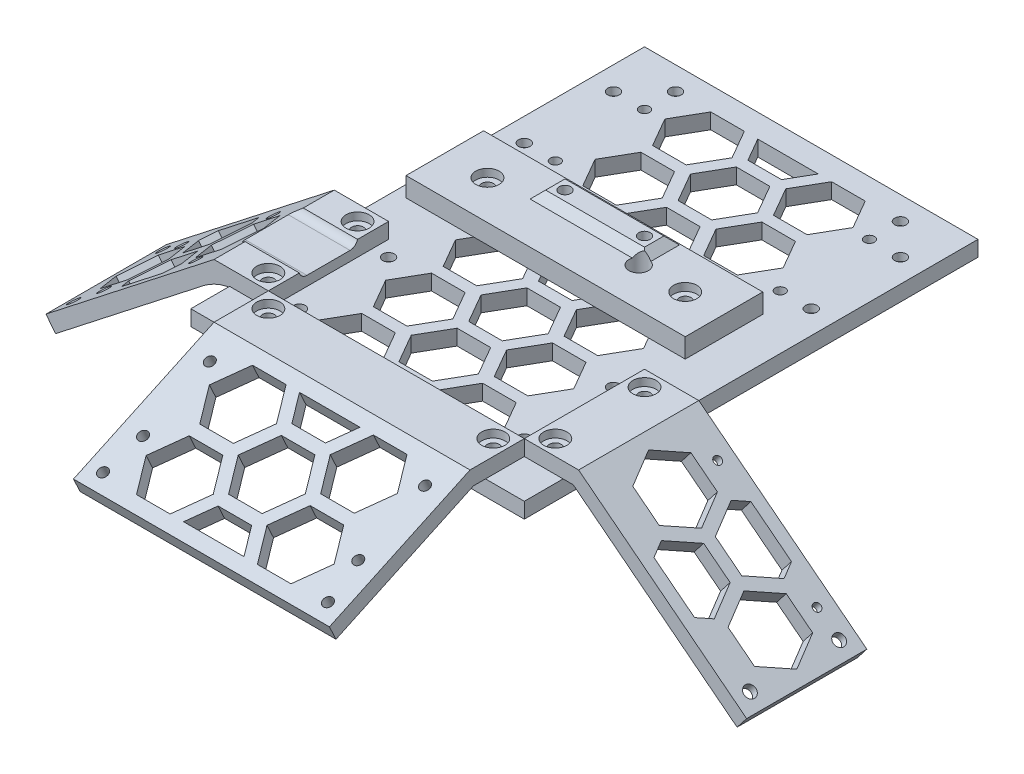
SolidWorks part; units mm, degrees
ref_plane "Front Plane" through (0, 0, 0) normal (0, 0, 1) x (1, 0, 0)
ref_plane "Top Plane" through (0, 0, 0) normal (0, 1, 0) x (1, 0, 0)
ref_plane "Right Plane" through (0, 0, 0) normal (1, 0, 0) x (0, 0, -1)
sketch "Sketch1" plane through (0, 0, 0) normal (0, 1, 0) x (1, 0, 0)
  line L0 (0, 0) -> (-19, 0) construction
  line L1 (0, 0) -> (23, 0) construction
  circle A0 centre (-25, 0) radius 6
  circle A1 centre (26, 0) radius 3
  dimension "D1" = 12
  dimension "D2" = 6
  dimension "D3" = 23
  dimension "D4" = 19
sketch "Sketch2" plane through (0, 0, 0) normal (0, 1, 0) x (1, 0, 0)
  line L0 (-36, 10) -> (-36, -10)
  line L1 (-36, -10) -> (36, -10)
  line L2 (36, -10) -> (36, 10)
  line L3 (36, 10) -> (-36, 10)
  line L4 (-31, 0) -> (-36, 0) construction
  line L5 (-36, -3.9429) -> (36, -3.9429) construction
  line L6 (0, 0) -> (-19, 0) construction
  line L7 (0, 0) -> (23, 0) construction
  circle A0 centre (-25, 0) radius 6 construction
  point P18 (0, -3.9429)
  dimension "D1" = 10
  dimension "D2" = 10
  dimension "D3" = 5
extrude "Boss-Extrude1" add sketch "Sketch2" along normal blind 5
extrude "Boss-Extrude2" add sketch "Sketch1" against normal blind 4
sketch "Sketch3" plane through (0, -4, 0) normal (0, -1, 0) x (1, 0, 0)
  circle A0 centre (-25, 0) radius 1.5
  circle A1 centre (26, 0) radius 1.5
  circle A2 centre (26, 0) radius 3 construction
  circle A3 centre (-25, 0) radius 6 construction
  dimension "D1" = 3
extrude "Cut-Extrude1" cut sketch "Sketch3" against normal through all
sketch "Sketch4" plane through (0, 5, 0) normal (0, 1, 0) x (1, 0, 0)
  circle A0 centre (-25, 0) radius 3
  circle A1 centre (26, 0) radius 3
  dimension "D1" = 6
extrude "Cut-Extrude2" cut sketch "Sketch4" against normal blind 2
sketch "Sketch5" plane through (0, 0, 0) normal (0, -1, 0) x (1, 0, 0)
  circle A0 centre (26, 0) radius 3
  circle A1 centre (26, 0) radius 4
  circle A2 centre (26, 0) radius 3 construction
  dimension "D1" = 8
extrude "Boss-Extrude3" [suppressed] add sketch "Sketch5" along normal blind 2.5
sketch "Sketch6" plane through (0, -4, 0) normal (0, -1, 0) x (1, 0, 0)
  line L0 (-36, 48.5) -> (-36, -48.5) construction
  line L1 (-36, -48.5) -> (36, -48.5) construction
  line L2 (36, -48.5) -> (36, 48.5) construction
  line L3 (36, 48.5) -> (-36, 48.5) construction
  line L4 (-36, 18.5) -> (36, 18.5) construction
  line L5 (-36, -18.5) -> (36, -18.5) construction
  line L6 (-36, -48.5) -> (-36, -58.5) construction
  line L7 (0, 18.5) -> (0, -18.5) construction
  line L8 (-36, 0) -> (36, 0) construction
  line L9 (-36, -10) -> (-36, 10) construction
  line L10 (-36, -58.5) -> (36, -58.5)
  line L11 (36, -58.5) -> (36, -48.5) construction
  line L12 (-36, 48.5) -> (-36, 58.5) construction
  line L13 (-36, 58.5) -> (36, 58.5)
  line L14 (36, 58.5) -> (36, 48.5) construction
  line L15 (-36, 58.5) -> (-43, 58.5)
  line L16 (-43, 58.5) -> (-43, -58.5)
  line L17 (-43, -58.5) -> (-36, -58.5)
  line L18 (36, -58.5) -> (43, -58.5)
  line L19 (43, -58.5) -> (43, 58.5)
  line L20 (43, 58.5) -> (36, 58.5)
  circle A0 centre (-29, -21.5) radius 1.3
  circle A2 centre (-29, -44.5) radius 1.3
  circle A3 centre (29, -44.5) radius 1.3
  circle A4 centre (29, -21.5) radius 1.3
  circle A5 centre (29, 21.5) radius 1.3 construction
  circle A6 centre (29, 44.5) radius 1.3 construction
  circle A7 centre (-29, 44.5) radius 1.3 construction
  circle A8 centre (-29, 21.5) radius 1.3 construction
  circle A9 centre (-25, 0) radius 1.5
  circle A10 centre (26, 0) radius 1.5
  circle A11 centre (26, 0) radius 1.5 construction
  circle A12 centre (-25, 0) radius 1.5 construction
  circle A13 centre (-29, 44.5) radius 1.5
  circle A14 centre (-29, 21.5) radius 1.5
  circle A15 centre (29, 21.5) radius 1.5
  circle A16 centre (29, 44.5) radius 1.5
  circle A17 centre (-29, 52.5) radius 1.5
  circle A18 centre (29, 52.5) radius 1.5
  circle A19 centre (29, -52.5) radius 1.5
  circle A20 centre (-29, -52.5) radius 1.5
  circle A21 centre (-37, 44.5) radius 1.5
  circle A22 centre (-37, 21.5) radius 1.5
  circle A23 centre (37, 44.5) radius 1.5
  circle A24 centre (37, 21.5) radius 1.5
  circle A25 centre (37, -44.5) radius 1.5
  circle A26 centre (37, -21.5) radius 1.5
  circle A27 centre (-37, -21.5) radius 1.5
  circle A28 centre (-37, -44.5) radius 1.5
  point P10 (0, 0)
  dimension "D2" = 29
  dimension "D4" = 2.6
  dimension "D5" = 23
  dimension "D8" = 3
  dimension "D11" = 3
  dimension "D13" = 7
  dimension "D15" = 8
  dimension "D1" = 37
  dimension "D3" = 3
  dimension "D6" = 4
  dimension "D7" = 4
  dimension "D9" = 10
  dimension "D10" = 10
  dimension "D14" = 8
extrude "Boss-Extrude4" add sketch "Sketch6" along normal blind 4 separate body
sketch "Sketch8" plane through (0, 0, 0) normal (0, -1, 0) x (1, 0, 0)
  circle A0 centre (14, 0) radius 2.5
  circle A1 centre (26, 0) radius 3 construction
  dimension "D1" = 5
  dimension "D2" = 12
extrude "Cut-Extrude3" cut sketch "Sketch8" against normal through all
sketch "Sketch10" plane through (0, 5, 0) normal (0, 1, 0) x (1, 0, 0)
  line L0 (-8.75, 5.25) -> (8.75, 5.25) construction
  line L1 (13, -7.5) -> (-13, -7.5) construction
  line L2 (13, -7.5) -> (13, 7.5) construction
  line L3 (13, 7.5) -> (-13, 7.5) construction
  line L4 (-13, -7.5) -> (-13, 7.5) construction
  line L5 (13, -7.5) -> (-13, 7.5) construction
  line L6 (13, 7.5) -> (-13, -7.5) construction
  line L7 (0, 5.25) -> (0, 0) construction
  line L8 (-8.75, 5.25) -> (-11.75, 5.25) construction
  line L9 (8.75, 5.25) -> (11.75, 5.25) construction
  line L10 (-10.25, 3.75) -> (-10.25, -7.5) construction
  line L11 (-10.25, 6.75) -> (-10.25, 7.5) construction
  line L12 (-11.75, 5.25) -> (-13, 5.25) construction
  circle A0 centre (-10.25, 5.25) radius 1.5
  circle A1 centre (10.25, 5.25) radius 1.5
  point P0 (0, 0)
  dimension "D3" = 23.5
  dimension "D4" = 3
  dimension "D5" = 3
  dimension "D1" = 26
  dimension "D2" = 15
  dimension "D6" = 11.25
extrude "Cut-Extrude4" cut sketch "Sketch10" against normal up to surface (5 mm away) up to face at (14, 0, -2.5)
sketch "Sketch11" plane through (0, 5, 0) normal (0, 1, 0) x (1, 0, 0)
  line L0 (-12.75, 7.75) -> (-12.75, 2.75)
  line L1 (-12.75, 2.75) -> (12.75, 2.75)
  line L2 (12.75, 2.75) -> (12.75, 7.75)
  line L3 (12.75, 7.75) -> (-12.75, 7.75)
  line L4 (0, 2.75) -> (0, 0) construction
  circle A0 centre (-10.25, 5.25) radius 1.5 construction
  circle A1 centre (10.25, 5.25) radius 1.5 construction
  circle A2 centre (-10.25, 5.25) radius 1.5
  circle A3 centre (10.25, 5.25) radius 1.5
  dimension "D1" = 2.5
  dimension "D2" = 2.5
  dimension "D3" = 2.5
extrude "Boss-Extrude6" add sketch "Sketch11" along normal blind 2
chamfer "Chamfer2" distance 2 angle 45 4 edges at (0, 5, -2.75) (12.75, 5, -5.25) (0, 5, -7.75) (-12.75, 5, -5.25)
sketch "Sketch12" plane through (0, 0, 0) normal (0, -1, 0) x (1, 0, 0)
  circle A0 centre (-10.25, -5.25) radius 3
  circle A1 centre (10.25, -5.25) radius 3
  dimension "D1" = 6
  dimension "D2" = 6
extrude "Cut-Extrude5" cut sketch "Sketch12" against normal blind 2
sketch "Sketch14" plane through (0, -8, 0) normal (0, -1, 0) x (1, 0, 0)
  line L0 (-37, 47.4831) -> (-31.9831, 47.4831)
  line L1 (-37, 41.5169) -> (-29, 41.5169)
  line L2 (-31.9831, 47.4831) -> (-31.9831, 52.5)
  line L3 (-26.0169, 44.5) -> (-26.0169, 52.5)
  line L4 (-37, 24.4831) -> (-29, 24.4831)
  line L5 (-37, 18.5169) -> (-29, 18.5169)
  line L6 (-43, 0) -> (43, 0) construction
  line L11 (0, 58.5) -> (0, -58.5) construction
  line L12 (43, 58.5) -> (-43, 58.5) construction
  line L13 (-43, -58.5) -> (43, -58.5) construction
  line L14 (37, 18.5169) -> (29, 18.5169)
  line L15 (37, 24.4831) -> (29, 24.4831)
  line L16 (26.0169, 44.5) -> (26.0169, 52.5)
  line L17 (31.9831, 47.4831) -> (31.9831, 52.5)
  line L18 (37, 41.5169) -> (29, 41.5169)
  line L19 (37, 47.4831) -> (31.9831, 47.4831)
  line L20 (37, -47.4831) -> (31.9831, -47.4831)
  line L21 (37, -41.5169) -> (29, -41.5169)
  line L22 (31.9831, -47.4831) -> (31.9831, -52.5)
  line L23 (26.0169, -44.5) -> (26.0169, -52.5)
  line L24 (37, -24.4831) -> (29, -24.4831)
  line L25 (37, -18.5169) -> (29, -18.5169)
  line L26 (-37, -18.5169) -> (-29, -18.5169)
  line L27 (-37, -24.4831) -> (-29, -24.4831)
  line L28 (-26.0169, -44.5) -> (-26.0169, -52.5)
  line L29 (-31.9831, -47.4831) -> (-31.9831, -52.5)
  line L30 (-37, -41.5169) -> (-29, -41.5169)
  line L31 (-37, -47.4831) -> (-31.9831, -47.4831)
  line L32 (-43, 58.5) -> (-43, -58.5) construction
  arc A0 (-29, 41.5169) -> (-26.0169, 44.5) centre (-29, 44.5) ccw
  arc A1 (-26.0169, 52.5) -> (-31.9831, 52.5) centre (-29, 52.5) ccw
  arc A2 (-37, 47.4831) -> (-37, 41.5169) centre (-37, 44.5) ccw
  arc A6 (-29, 18.5169) -> (-29, 24.4831) centre (-29, 21.5) ccw
  arc A7 (-37, 24.4831) -> (-37, 18.5169) centre (-37, 21.5) ccw
  circle A10 centre (-25, 0) radius 2.9831
  circle A11 centre (26, 0) radius 2.9831
  arc A12 (37, 24.4831) -> (37, 18.5169) centre (37, 21.5) cw
  arc A13 (29, 18.5169) -> (29, 24.4831) centre (29, 21.5) cw
  arc A14 (37, 47.4831) -> (37, 41.5169) centre (37, 44.5) cw
  arc A15 (26.0169, 52.5) -> (31.9831, 52.5) centre (29, 52.5) cw
  arc A16 (29, 41.5169) -> (26.0169, 44.5) centre (29, 44.5) cw
  arc A17 (29, -41.5169) -> (26.0169, -44.5) centre (29, -44.5) ccw
  arc A18 (26.0169, -52.5) -> (31.9831, -52.5) centre (29, -52.5) ccw
  arc A19 (37, -47.4831) -> (37, -41.5169) centre (37, -44.5) ccw
  arc A20 (29, -18.5169) -> (29, -24.4831) centre (29, -21.5) ccw
  arc A21 (37, -24.4831) -> (37, -18.5169) centre (37, -21.5) ccw
  arc A22 (-37, -24.4831) -> (-37, -18.5169) centre (-37, -21.5) cw
  arc A23 (-29, -18.5169) -> (-29, -24.4831) centre (-29, -21.5) cw
  arc A24 (-37, -47.4831) -> (-37, -41.5169) centre (-37, -44.5) cw
  arc A25 (-26.0169, -52.5) -> (-31.9831, -52.5) centre (-29, -52.5) cw
  arc A26 (-29, -41.5169) -> (-26.0169, -44.5) centre (-29, -44.5) cw
extrude "Cut-Extrude6" cut sketch "Sketch14" against normal blind 2
sketch "Sketch15" plane through (0, -4, 0) normal (0, 1, 0) x (1, 0, 0)
  line L0 (-33, -17.5) -> (-33, -48.5)
  line L1 (-33, -48.5) -> (-47, -48.5)
  line L2 (-47, -48.5) -> (-47, -17.5)
  line L3 (-47, -17.5) -> (-33, -17.5)
  line L4 (-43, -58.5) -> (-43, 58.5) construction
  circle A0 centre (-37, -21.5) radius 1.5
  circle A1 centre (-37, -44.5) radius 1.5
  circle A2 centre (-37, -21.5) radius 1.5 construction
  circle A3 centre (-37, -44.5) radius 1.5 construction
  dimension "D1" = 4
  dimension "D2" = 4
  dimension "D3" = 4
  dimension "D4" = 4
extrude "Boss-Extrude7" add sketch "Sketch15" along normal blind 4 separate body
sketch "Sketch17" plane through (0, 0, 48.5) normal (0, 0, 1) x (1, 0, 0)
  line L0 (-47, 0) -> (-90.3406, -33.8614)
  line L1 (-90.3406, -33.8614) -> (-87.8779, -37.0134)
  line L2 (-87.8779, -37.0134) -> (-45.6227, -4)
  line L3 (-47, -4) -> (-33, -4) construction
  line L4 (-45.6227, -4) -> (-47, 0)
  dimension "D1" = 38
  dimension "D2" = 4
  dimension "D3" = 55
extrude "Boss-Extrude8" add sketch "Sketch17" against normal up to surface (31 mm away) up to face at (-40, -2, 17.5)
sketch "Sketch18" plane through (0, 0, 0) normal (0, 1, 0) x (1, 0, 0)
  circle A0 centre (-37, -21.5) radius 3
  circle A1 centre (-37, -44.5) radius 3
  dimension "D1" = 6
  dimension "D2" = 6
extrude "Cut-Extrude7" cut sketch "Sketch18" against normal blind 2
sketch "Sketch19" plane through (-17.8148, 22.8019, 0) normal (-0.6157, 0.788, 0) x (0.788, 0.6157, 0)
  line L0 (-37.0365, -17.5) -> (-37.0365, -48.5) construction
  line L1 (-80.0365, -23) -> (-50.0365, -23) construction
  line L2 (-80.0365, -23) -> (-80.0365, -43) construction
  line L3 (-80.0365, -43) -> (-50.0365, -43) construction
  line L4 (-50.0365, -23) -> (-50.0365, -43) construction
  line L5 (-80.0365, -23) -> (-50.0365, -43) construction
  line L6 (-80.0365, -43) -> (-50.0365, -23) construction
  line L7 (-88.0365, -21.5) -> (-29.2057, -21.5) construction
  line L8 (-88.0365, -44.5) -> (-29.2057, -44.5) construction
  line L9 (-92.0365, -17.5) -> (-92.0365, -48.5) construction
  circle A0 centre (-50.0365, -23) radius 1.5
  circle A1 centre (-50.0365, -43) radius 1.5
  circle A2 centre (-80.0365, -43) radius 1.5
  circle A3 centre (-80.0365, -23) radius 1.5
  circle A4 centre (-88.0365, -21.5) radius 1.5
  circle A5 centre (-88.0365, -44.5) radius 1.5
  ellipse E1 centre (-30.3877, -21.5) end of major axis (-30.3877, -23) minor radius 1.182 construction
  ellipse E2 centre (-30.3877, -44.5) end of major axis (-30.3877, -46) minor radius 1.182 construction
  point P0 (-65.0365, -33)
  point P7 (-37.0365, -33)
  dimension "D3" = 3
  dimension "D5" = 3
  dimension "D1" = 30
  dimension "D2" = 20
  dimension "D4" = 28
  dimension "D6" = 4
extrude "Cut-Extrude8" cut sketch "Sketch19" against normal through all
sketch "Sketch20" plane through (-15.3522, 19.6499, 0) normal (0.6157, -0.788, 0) x (0.788, 0.6157, 0)
  line L0 (-88.5894, 24.4486) -> (-80.5894, 25.9486)
  line L1 (-87.4836, 18.5514) -> (-79.4836, 20.0514)
  line L2 (-88.5894, 41.5514) -> (-80.5894, 40.0514)
  line L3 (-87.4836, 47.4486) -> (-79.4836, 45.9486)
  arc A0 (-87.4836, 47.4486) -> (-88.5894, 41.5514) centre (-88.0365, 44.5) ccw
  arc A1 (-88.5894, 24.4486) -> (-87.4836, 18.5514) centre (-88.0365, 21.5) ccw
  arc A2 (-79.4836, 20.0514) -> (-80.5894, 25.9486) centre (-80.0365, 23) ccw
  arc A3 (-80.5894, 40.0514) -> (-79.4836, 45.9486) centre (-80.0365, 43) ccw
  circle A4 centre (-50.0365, 43) radius 3
  circle A5 centre (-50.0365, 23) radius 3
  dimension "D1" = 6
  dimension "D2" = 6
  dimension "D3" = 6
  dimension "D4" = 6
  dimension "D5" = 6
extrude "Cut-Extrude9" cut sketch "Sketch20" against normal blind 2
sketch "Sketch21" plane through (0, -4, 0) normal (0, 1, 0) x (1, 0, 0)
  line L0 (-33, -48.5) -> (-33, -62.5)
  line L1 (-33, -62.5) -> (33, -62.5)
  line L2 (33, -62.5) -> (33, -48.5)
  line L3 (33, -48.5) -> (-33, -48.5)
  line L5 (43, -58.5) -> (-43, -58.5) construction
  circle A0 centre (-29, -52.5) radius 1.5 construction
  circle A2 centre (29, -52.5) radius 1.5 construction
  circle A3 centre (-29, -52.5) radius 1.5
  circle A4 centre (29, -52.5) radius 1.5
  dimension "D3" = 4
  dimension "D1" = 4
  dimension "D2" = 4
  dimension "D4" = 4
extrude "Boss-Extrude9" add sketch "Sketch21" along normal blind 4 separate body
sketch "Sketch22" plane through (0, 0, 0) normal (0, 1, 0) x (1, 0, 0)
  circle A0 centre (-29, -52.5) radius 3
  circle A1 centre (29, -52.5) radius 3
  dimension "D1" = 6
  dimension "D2" = 6
extrude "Cut-Extrude10" cut sketch "Sketch22" against normal blind 2
sketch "Sketch23" plane through (-33, 0, 0) normal (-1, 0, 0) x (0, 0, 1)
  line L0 (62.5, 0) -> (98.7523, -16.9047)
  line L1 (98.7523, -16.9047) -> (97.0618, -20.53)
  line L2 (97.0618, -20.53) -> (61.6132, -4)
  line L3 (48.5, -4) -> (62.5, -4) construction
  line L5 (61.6132, -4) -> (62.5, 0)
  dimension "D1" = 4
  dimension "D2" = 25
  dimension "D3" = 40
extrude "Boss-Extrude10" add sketch "Sketch23" against normal up to surface (66 mm away) up to face at (33, -2, 55.5)
sketch "Sketch25" plane through (0, 0, 0) normal (0, 1, 0) x (1, 0, 0)
  line L0 (-33, -25.5) -> (-90.3406, -25.5)
  line L1 (-33, -48.5) -> (-33, -17.5) construction
  line L2 (-90.3406, -17.5) -> (-90.3406, -48.5) construction
  line L3 (-90.3406, -25.5) -> (-90.3406, -40.5)
  line L4 (-90.3406, -40.5) -> (-33, -40.5)
  line L5 (-33, -40.5) -> (-33, -25.5)
  circle A0 centre (-37, -21.5) radius 3 construction
  circle A1 centre (-37, -44.5) radius 3 construction
  dimension "D1" = 4
  dimension "D2" = 4
extrude "Cut-Extrude11" cut sketch "Sketch25" against normal blind 1.5
fillet "Fillet1" radius 2 2 edges at (-40.96, -1.5, 40.5) (-40.96, -1.5, 25.5)
fillet "Fillet2" radius 15 1 edges at (-45.6227, -4, 33)
sketch "Sketch28" plane through (0, 23.9389, 11.1629) normal (0, 0.9063, 0.4226) x (1, 0, 0)
  line L0 (33, -96.6442) -> (-33, -96.6442) construction
  line L1 (-29, -47.0669) -> (-29, -92.6442) construction
  line L2 (0, -43.9559) -> (0, -96.6442) construction
  line L3 (33, -43.9559) -> (-33, -43.9559) construction
  line L4 (-33, -56.6442) -> (33, -56.6442) construction
  line L5 (-27.75, -63.6442) -> (27.75, -63.6442) construction
  line L6 (-27.75, -63.6442) -> (-27.75, -82.6442) construction
  line L7 (-27.75, -82.6442) -> (27.75, -82.6442) construction
  line L8 (27.75, -63.6442) -> (27.75, -82.6442) construction
  line L9 (-27.75, -63.6442) -> (27.75, -82.6442) construction
  line L10 (-27.75, -82.6442) -> (27.75, -63.6442) construction
  circle A0 centre (-29, -92.6442) radius 1.25
  circle A1 centre (29, -92.6442) radius 1.25
  circle A2 centre (-27.75, -63.6442) radius 1.25
  circle A3 centre (-27.75, -82.6442) radius 1.25
  circle A4 centre (27.75, -82.6442) radius 1.25
  circle A5 centre (27.75, -63.6442) radius 1.25
  ellipse E0 centre (-29, -48.4264) end of major axis (-27.5, -48.4264) minor radius 1.3595 construction
  point P17 (0, -73.1442)
  dimension "D1" = 4
  dimension "D2" = 2.5
  dimension "D5" = 2.5
  dimension "D3" = 55.5
  dimension "D4" = 19
  dimension "D6" = 7
extrude "Cut-Extrude12" cut sketch "Sketch28" against normal up to surface (4 mm away) up to face at (0, -12.265, 79.3375)
sketch "Sketch29" plane through (0, 23.9389, 11.1629) normal (0, 0.9063, 0.4226) x (1, 0, 0)
  line L0 (-33, -76.6442) -> (33, -76.6442) construction
  line L1 (-6.9282, -67.6442) -> (-11.2583, -60.1442)
  line L2 (-11.2583, -60.1442) -> (-19.9186, -60.1442)
  line L3 (-19.9186, -60.1442) -> (-24.2487, -67.6442)
  line L4 (-24.2487, -67.6442) -> (-19.9186, -75.1442)
  line L5 (-19.9186, -75.1442) -> (-11.2583, -75.1442)
  line L6 (-11.2583, -75.1442) -> (-6.9282, -67.6442)
  line L7 (24.2487, -67.6442) -> (19.9186, -60.1442)
  line L8 (19.9186, -60.1442) -> (11.2583, -60.1442)
  line L9 (11.2583, -60.1442) -> (6.9282, -67.6442)
  line L10 (6.9282, -67.6442) -> (11.2583, -75.1442)
  line L11 (11.2583, -75.1442) -> (19.9186, -75.1442)
  line L12 (19.9186, -75.1442) -> (24.2487, -67.6442)
  line L13 (8.6603, -76.6442) -> (4.3301, -69.1442)
  line L14 (4.3301, -69.1442) -> (-4.3301, -69.1442)
  line L15 (-4.3301, -69.1442) -> (-8.6603, -76.6442)
  line L16 (-8.6603, -76.6442) -> (-4.3301, -84.1442)
  line L17 (-4.3301, -84.1442) -> (4.3301, -84.1442)
  line L18 (4.3301, -84.1442) -> (8.6603, -76.6442)
  line L19 (24.2487, -85.6442) -> (19.9186, -78.1442)
  line L20 (19.9186, -78.1442) -> (11.2583, -78.1442)
  line L21 (11.2583, -78.1442) -> (6.9282, -85.6442)
  line L22 (6.9282, -85.6442) -> (11.2583, -93.1442)
  line L23 (11.2583, -93.1442) -> (19.9186, -93.1442)
  line L24 (19.9186, -93.1442) -> (24.2487, -85.6442)
  line L25 (-6.9282, -85.6442) -> (-11.2583, -78.1442)
  line L26 (-11.2583, -78.1442) -> (-19.9186, -78.1442)
  line L27 (-19.9186, -78.1442) -> (-24.2487, -85.6442)
  line L28 (-24.2487, -85.6442) -> (-19.9186, -93.1442)
  line L29 (-19.9186, -93.1442) -> (-11.2583, -93.1442)
  line L30 (-11.2583, -93.1442) -> (-6.9282, -85.6442)
  line L31 (-33, -96.6442) -> (-33, -56.6442) construction
  line L32 (33, -56.6442) -> (33, -96.6442) construction
  line L33 (-7.7942, -93.1442) -> (7.7942, -93.1442)
  line L34 (7.7942, -93.1442) -> (4.3301, -87.1442)
  line L35 (4.3301, -87.1442) -> (-4.3301, -87.1442)
  line L36 (-4.3301, -87.1442) -> (-7.7942, -93.1442)
  line L40 (-7.7942, -60.1442) -> (7.7942, -60.1442)
  line L41 (-8.6603, -94.6442) -> (-6.4952, -98.3942) [skipped]
  line L42 (4.3301, -102.1442) -> (6.4952, -98.3942) [skipped]
  line L43 (-4.3301, -102.1442) -> (0, -102.1442) [skipped]
  line L44 (-4.3301, -66.1442) -> (-7.7942, -60.1442)
  line L45 (4.3301, -66.1442) -> (-4.3301, -66.1442)
  line L46 (7.7942, -60.1442) -> (4.3301, -66.1442)
  circle A0 centre (-15.5885, -67.6442) radius 7.5 construction
  circle A1 centre (15.5885, -67.6442) radius 7.5 construction
  circle A2 centre (0, -76.6442) radius 7.5 construction
  circle A3 centre (15.5885, -85.6442) radius 7.5 construction
  circle A4 centre (-15.5885, -85.6442) radius 7.5 construction
  arc A6 (7.3485, -93.1442) -> (-7.3485, -93.1442) centre (0, -94.6442) ccw construction
  dimension "D1" = 15
  dimension "D8" = 3
  dimension "D2" = 3
  dimension "D3" = 1.5
  dimension "D4" = 3
  dimension "D5" = 3
  dimension "D6" = 3
  dimension "D7" = 3
  dimension "D9" = 3
  dimension "D10" = 3
  dimension "D11" = 3
extrude "Cut-Extrude13" cut sketch "Sketch29" against normal up to surface (4 mm away) up to face at (27.75, -14.085, 83.2406)
sketch "Sketch30" plane through (0, -4, 0) normal (0, 1, 0) x (1, 0, 0)
  line L0 (33, -48.5) -> (47, -48.5)
  line L1 (47, -48.5) -> (47, -17.5)
  line L2 (47, -17.5) -> (33, -17.5)
  line L3 (33, -17.5) -> (33, -48.5)
  line L4 (-33, -17.5) -> (-47, -17.5) construction
  circle A0 centre (37, -21.5) radius 1.5
  circle A2 centre (37, -44.5) radius 1.5
  circle A4 centre (-37, -44.5) radius 1.5 construction
extrude "Boss-Extrude11" add sketch "Sketch30" along normal blind 4 separate body
sketch "Sketch31" plane through (0, 0, 48.5) normal (0, 0, 1) x (1, 0, 0)
  line L0 (47, 0) -> (90.3406, -33.8614)
  line L1 (90.3406, -33.8614) -> (87.8779, -37.0134)
  line L2 (87.8779, -37.0134) -> (45.6227, -4)
  line L3 (33, -4) -> (47, -4) construction
  line L4 (47, 0) -> (45.6227, -4)
  line L5 (-90.3406, -33.8614) -> (-87.8779, -37.0134) construction
  line L6 (-47, 0) -> (-90.3406, -33.8614) construction
  dimension "D1" = 38
extrude "Boss-Extrude12" add sketch "Sketch31" against normal up to surface (31 mm away) up to face at (40, -2, 17.5)
sketch "Sketch32" plane through (17.8148, 22.8019, 0) normal (0.6157, 0.788, 0) x (0.788, -0.6157, 0)
  line L0 (92.0365, -17.5) -> (92.0365, -48.5) construction
  line L1 (27.9744, -21.5) -> (88.0365, -21.5) construction
  line L2 (88.0365, -21.5) -> (88.0365, -44.5) construction
  line L3 (88.0365, -44.5) -> (27.9744, -44.5) construction
  line L4 (48.2865, -21.5) -> (80.7865, -21.5) construction
  line L5 (37.0365, -33) -> (92.0365, -33) construction
  line L6 (37.0365, -48.5) -> (37.0365, -17.5) construction
  line L7 (64.5365, -21.5) -> (64.5365, -33) construction
  circle A0 centre (88.0365, -21.5) radius 1.5
  circle A1 centre (88.0365, -44.5) radius 1.5
  circle A2 centre (48.2865, -21.5) radius 1
  circle A3 centre (80.7865, -21.5) radius 1
  ellipse E0 centre (29.1564, -21.5) end of major axis (29.1564, -20) minor radius 1.182 construction
  ellipse E1 centre (29.1564, -44.5) end of major axis (29.1564, -43) minor radius 1.182 construction
  dimension "D1" = 4
  dimension "D2" = 3
  dimension "D3" = 32.5
  dimension "D4" = 2
  dimension "D5" = 2
extrude "Cut-Extrude14" cut sketch "Sketch32" against normal up to surface (4 mm away) up to face at (66.7503, -20.5067, 33)
sketch "Sketch33" plane through (17.8148, 22.8019, 0) normal (0.6157, 0.788, 0) x (0.788, -0.6157, 0)
  line L0 (37.0365, -33) -> (92.0365, -33) construction
  line L1 (57.6083, -33) -> (53.2782, -25.5)
  line L2 (53.2782, -25.5) -> (44.6179, -25.5)
  line L3 (44.6179, -25.5) -> (40.2878, -33)
  line L4 (40.2878, -33) -> (44.6179, -40.5)
  line L5 (44.6179, -40.5) -> (53.2782, -40.5)
  line L6 (53.2782, -40.5) -> (57.6083, -33)
  line L7 (88.7852, -33) -> (84.4551, -25.5)
  line L8 (84.4551, -25.5) -> (75.7948, -25.5)
  line L9 (75.7948, -25.5) -> (71.4647, -33)
  line L10 (71.4647, -33) -> (75.7948, -40.5)
  line L11 (75.7948, -40.5) -> (84.4551, -40.5)
  line L12 (84.4551, -40.5) -> (88.7852, -33)
  line L13 (37.0365, -48.5) -> (37.0365, -17.5) construction
  line L14 (92.0365, -17.5) -> (92.0365, -48.5) construction
  line L15 (57.897, -45.5) -> (71.176, -45.5)
  line L16 (73.1968, -42) -> (68.8666, -34.5)
  line L17 (68.8666, -34.5) -> (60.2064, -34.5)
  line L18 (60.2064, -34.5) -> (55.8763, -42)
  line L19 (55.8763, -42) -> (57.897, -45.5)
  line L21 (71.176, -45.5) -> (73.1968, -42)
  line L22 (73.1968, -24) -> (71.176, -20.5)
  line L24 (57.897, -20.5) -> (55.8763, -24)
  line L25 (55.8763, -24) -> (60.2064, -31.5)
  line L26 (60.2064, -31.5) -> (68.8666, -31.5)
  line L27 (68.8666, -31.5) -> (73.1968, -24)
  line L28 (92.0365, -48.5) -> (37.0365, -48.5) construction
  line L29 (57.897, -20.5) -> (71.176, -20.5)
  line L30 (37.0365, -17.5) -> (92.0365, -17.5) construction
  line L31 (68.8666, -16.5) -> (64.5365, -16.5) [skipped]
  line L32 (60.2064, -49.5) -> (64.5365, -49.5) [skipped]
  circle A0 centre (48.948, -33) radius 7.5 construction
  circle A1 centre (80.125, -33) radius 7.5 construction
  arc A2 (71.1698, -45.5) -> (57.9033, -45.5) centre (64.5365, -42) ccw construction
  arc A3 (57.9033, -20.5) -> (71.1698, -20.5) centre (64.5365, -24) ccw construction
  point P39 (64.5365, -33)
  dimension "D1" = 15
  dimension "D2" = 15
  dimension "D3" = 3
  dimension "D4" = 3
  dimension "D5" = 3
  dimension "D6" = 3
  dimension "D7" = 3
  dimension "D8" = 3
  dimension "D9" = 3
extrude "Cut-Extrude15" cut sketch "Sketch33" against normal up to surface (4 mm away) up to face at (54.1905, -10.6939, 21.5)
sketch "Sketch34" plane through (15.3522, 19.6499, 0) normal (-0.6157, -0.788, 0) x (0.788, -0.6157, 0)
  circle A0 centre (88.0365, 44.5) radius 3
  circle A1 centre (88.0365, 21.5) radius 3
  circle A2 centre (80.7865, 21.5) radius 2.5
  circle A5 centre (48.2865, 21.5) radius 2.5
  dimension "D1" = 5
  dimension "D2" = 6
extrude "Cut-Extrude16" cut sketch "Sketch34" against normal blind 2
sketch "Sketch35" plane through (-17.8148, 22.8019, 0) normal (-0.6157, 0.788, 0) x (0.788, 0.6157, 0)
  line L0 (-37.0365, -48.5) -> (-37.0365, -17.5) construction
  line L1 (-92.0365, -33) -> (-37.0365, -33) construction
  line L2 (-92.0365, -17.5) -> (-92.0365, -48.5) construction
  line L3 (-64.5365, -24) -> (-64.5365, -33) construction
  line L4 (-55.8763, -24) -> (-57.897, -20.5)
  line L6 (-71.176, -20.5) -> (-73.1968, -24)
  line L7 (-73.1968, -24) -> (-68.8666, -31.5)
  line L8 (-68.8666, -31.5) -> (-60.2064, -31.5)
  line L9 (-60.2064, -31.5) -> (-55.8763, -24)
  line L10 (-40.2878, -33) -> (-44.6179, -25.5)
  line L11 (-44.6179, -25.5) -> (-53.2782, -25.5)
  line L12 (-53.2782, -25.5) -> (-57.6083, -33)
  line L13 (-57.6083, -33) -> (-53.2782, -40.5)
  line L14 (-53.2782, -40.5) -> (-44.6179, -40.5)
  line L15 (-44.6179, -40.5) -> (-40.2878, -33)
  line L16 (-71.4647, -33) -> (-75.7948, -25.5)
  line L17 (-75.7948, -25.5) -> (-84.4551, -25.5)
  line L18 (-84.4551, -25.5) -> (-88.7852, -33)
  line L19 (-88.7852, -33) -> (-84.4551, -40.5)
  line L20 (-84.4551, -40.5) -> (-75.7948, -40.5)
  line L21 (-75.7948, -40.5) -> (-71.4647, -33)
  line L22 (-55.8763, -42) -> (-60.2064, -34.5)
  line L23 (-60.2064, -34.5) -> (-68.8666, -34.5)
  line L24 (-68.8666, -34.5) -> (-73.1968, -42)
  line L25 (-73.1968, -42) -> (-71.176, -45.5)
  line L27 (-57.897, -45.5) -> (-55.8763, -42)
  line L28 (-71.176, -20.5) -> (-57.897, -20.5)
  line L29 (45.2956, -20.5) -> (42.0831, -20.5) construction
  line L32 (-71.176, -45.5) -> (-57.897, -45.5)
  line L33 (42.0831, -45.5) -> (45.2956, -45.5) construction
  line L34 (-68.8666, -49.5) -> (-64.5365, -49.5) [skipped]
  line L35 (-64.6684, -16.5) -> (-68.9985, -16.5) [skipped]
  arc A0 (-71.1698, -20.5) -> (-57.9033, -20.5) centre (-64.5365, -24) ccw construction
  circle A1 centre (-48.948, -33) radius 7.5 construction
  circle A2 centre (-80.125, -33) radius 7.5 construction
  arc A3 (-57.9033, -45.5) -> (-71.1698, -45.5) centre (-64.5365, -42) ccw construction
  dimension "D2" = 15
  dimension "D1" = 3
  dimension "D3" = 3
  dimension "D4" = 3
  dimension "D5" = 3
  dimension "D6" = 3
extrude "Cut-Extrude17" cut sketch "Sketch35" against normal up to surface (4 mm away) up to face at (-81.5739, -32.0881, 43.75)
sketch "Sketch36" plane through (0, -4, 0) normal (0, 1, 0) x (1, 0, 0)
  line L0 (8.6603, -18) -> (4.3301, -10.5)
  line L1 (8.6603, 0) -> (4.3301, 7.5)
  line L2 (4.3301, 7.5) -> (-4.3301, 7.5)
  line L3 (-4.3301, 7.5) -> (-8.6603, 0)
  line L4 (-8.6603, 0) -> (-4.3301, -7.5)
  line L5 (-4.3301, -7.5) -> (4.3301, -7.5)
  line L6 (4.3301, -7.5) -> (8.6603, 0)
  line L7 (-6.9282, 9) -> (-11.2583, 16.5)
  line L8 (-11.2583, 16.5) -> (-19.9186, 16.5)
  line L9 (-19.9186, 16.5) -> (-24.2487, 9)
  line L10 (-24.2487, 9) -> (-19.9186, 1.5)
  line L11 (-19.9186, 1.5) -> (-11.2583, 1.5)
  line L12 (-11.2583, 1.5) -> (-6.9282, 9)
  line L13 (24.2487, 9) -> (19.9186, 16.5)
  line L14 (19.9186, 16.5) -> (11.2583, 16.5)
  line L15 (11.2583, 16.5) -> (6.9282, 9)
  line L16 (6.9282, 9) -> (11.2583, 1.5)
  line L17 (11.2583, 1.5) -> (19.9186, 1.5)
  line L18 (19.9186, 1.5) -> (24.2487, 9)
  line L19 (4.3301, -10.5) -> (-4.3301, -10.5)
  line L20 (-4.3301, -10.5) -> (-8.6603, -18)
  line L21 (-8.6603, -18) -> (-4.3301, -25.5)
  line L22 (-4.3301, -25.5) -> (4.3301, -25.5)
  line L23 (4.3301, -25.5) -> (8.6603, -18)
  line L24 (-6.9282, -9) -> (-11.2583, -1.5)
  line L25 (-11.2583, -1.5) -> (-19.9186, -1.5)
  line L26 (-19.9186, -1.5) -> (-24.2487, -9)
  line L27 (-24.2487, -9) -> (-19.9186, -16.5)
  line L28 (-19.9186, -16.5) -> (-11.2583, -16.5)
  line L29 (-11.2583, -16.5) -> (-6.9282, -9)
  line L30 (24.2487, -9) -> (19.9186, -1.5)
  line L31 (19.9186, -1.5) -> (11.2583, -1.5)
  line L32 (11.2583, -1.5) -> (6.9282, -9)
  line L33 (6.9282, -9) -> (11.2583, -16.5)
  line L34 (11.2583, -16.5) -> (19.9186, -16.5)
  line L35 (19.9186, -16.5) -> (24.2487, -9)
  line L36 (8.6603, -36) -> (4.3301, -28.5)
  line L37 (4.3301, -28.5) -> (-4.3301, -28.5)
  line L38 (-4.3301, -28.5) -> (-8.6603, -36)
  line L39 (-8.6603, -36) -> (-4.3301, -43.5)
  line L40 (-4.3301, -43.5) -> (4.3301, -43.5)
  line L41 (4.3301, -43.5) -> (8.6603, -36)
  line L42 (-6.9282, -27) -> (-11.2583, -19.5)
  line L43 (-11.2583, -19.5) -> (-19.9186, -19.5)
  line L44 (-19.9186, -19.5) -> (-24.2487, -27)
  line L45 (-24.2487, -27) -> (-19.9186, -34.5)
  line L46 (-19.9186, -34.5) -> (-11.2583, -34.5)
  line L47 (-11.2583, -34.5) -> (-6.9282, -27)
  line L48 (24.2487, -27) -> (19.9186, -19.5)
  line L49 (19.9186, -19.5) -> (11.2583, -19.5)
  line L50 (11.2583, -19.5) -> (6.9282, -27)
  line L51 (6.9282, -27) -> (11.2583, -34.5)
  line L52 (11.2583, -34.5) -> (19.9186, -34.5)
  line L53 (19.9186, -34.5) -> (24.2487, -27)
  line L54 (8.6603, -54) -> (4.3301, -46.5)
  line L55 (4.3301, -46.5) -> (-4.3301, -46.5)
  line L56 (-4.3301, -46.5) -> (-8.6603, -54)
  line L57 (-8.6603, -54) -> (-4.3301, -61.5)
  line L58 (-4.3301, -61.5) -> (4.3301, -61.5)
  line L59 (4.3301, -61.5) -> (8.6603, -54)
  line L60 (-6.9282, -45) -> (-11.2583, -37.5)
  line L61 (-11.2583, -37.5) -> (-19.9186, -37.5)
  line L62 (-19.9186, -37.5) -> (-24.2487, -45)
  line L63 (-24.2487, -45) -> (-19.9186, -52.5)
  line L64 (-19.9186, -52.5) -> (-11.2583, -52.5)
  line L65 (-11.2583, -52.5) -> (-6.9282, -45)
  line L66 (24.2487, -45) -> (19.9186, -37.5)
  line L67 (19.9186, -37.5) -> (11.2583, -37.5)
  line L68 (11.2583, -37.5) -> (6.9282, -45)
  line L69 (6.9282, -45) -> (11.2583, -52.5)
  line L70 (11.2583, -52.5) -> (19.9186, -52.5)
  line L71 (19.9186, -52.5) -> (24.2487, -45)
  line L72 (8.6603, -72) -> (4.3301, -64.5)
  line L73 (4.3301, -64.5) -> (-4.3301, -64.5)
  line L74 (-4.3301, -64.5) -> (-8.6603, -72)
  line L75 (-8.6603, -72) -> (-4.3301, -79.5)
  line L76 (-4.3301, -79.5) -> (4.3301, -79.5)
  line L77 (4.3301, -79.5) -> (8.6603, -72)
  line L78 (-6.9282, -63) -> (-11.2583, -55.5)
  line L79 (-11.2583, -55.5) -> (-19.9186, -55.5)
  line L80 (-19.9186, -55.5) -> (-24.2487, -63)
  line L81 (-24.2487, -63) -> (-19.9186, -70.5)
  line L82 (-19.9186, -70.5) -> (-11.2583, -70.5)
  line L83 (-11.2583, -70.5) -> (-6.9282, -63)
  line L84 (24.2487, -63) -> (19.9186, -55.5)
  line L85 (19.9186, -55.5) -> (11.2583, -55.5)
  line L86 (11.2583, -55.5) -> (6.9282, -63)
  line L87 (6.9282, -63) -> (11.2583, -70.5)
  line L88 (11.2583, -70.5) -> (19.9186, -70.5)
  line L89 (19.9186, -70.5) -> (24.2487, -63)
  line L90 (8.6603, 0) -> (4.3301, 7.5)
  line L91 (4.3301, 7.5) -> (-4.3301, 7.5)
  line L92 (-4.3301, 7.5) -> (-8.6603, 0)
  line L93 (-8.6603, 0) -> (-4.3301, -7.5)
  line L94 (-4.3301, -7.5) -> (4.3301, -7.5)
  line L95 (4.3301, -7.5) -> (8.6603, 0)
  line L96 (-6.9282, 9) -> (-11.2583, 16.5)
  line L97 (-11.2583, 16.5) -> (-19.9186, 16.5)
  line L98 (-19.9186, 16.5) -> (-24.2487, 9)
  line L99 (-24.2487, 9) -> (-19.9186, 1.5)
  line L100 (-19.9186, 1.5) -> (-11.2583, 1.5)
  line L101 (-11.2583, 1.5) -> (-6.9282, 9)
  line L102 (24.2487, 9) -> (19.9186, 16.5)
  line L103 (19.9186, 16.5) -> (11.2583, 16.5)
  line L104 (11.2583, 16.5) -> (6.9282, 9)
  line L105 (6.9282, 9) -> (11.2583, 1.5)
  line L106 (11.2583, 1.5) -> (19.9186, 1.5)
  line L107 (19.9186, 1.5) -> (24.2487, 9)
  line L108 (8.6603, -18) -> (4.3301, -10.5)
  line L109 (4.3301, -10.5) -> (-4.3301, -10.5)
  line L110 (-4.3301, -10.5) -> (-8.6603, -18)
  line L111 (-8.6603, -18) -> (-4.3301, -25.5)
  line L112 (-4.3301, -25.5) -> (4.3301, -25.5)
  line L113 (4.3301, -25.5) -> (8.6603, -18)
  line L114 (-6.9282, -9) -> (-11.2583, -1.5)
  line L115 (-11.2583, -1.5) -> (-19.9186, -1.5)
  line L116 (-19.9186, -1.5) -> (-24.2487, -9)
  line L117 (-24.2487, -9) -> (-19.9186, -16.5)
  line L118 (-19.9186, -16.5) -> (-11.2583, -16.5)
  line L119 (-11.2583, -16.5) -> (-6.9282, -9)
  line L120 (24.2487, -9) -> (19.9186, -1.5)
  line L121 (19.9186, -1.5) -> (11.2583, -1.5)
  line L122 (11.2583, -1.5) -> (6.9282, -9)
  line L123 (6.9282, -9) -> (11.2583, -16.5)
  line L124 (11.2583, -16.5) -> (19.9186, -16.5)
  line L125 (19.9186, -16.5) -> (24.2487, -9)
  line L126 (8.6603, -36) -> (4.3301, -28.5)
  line L127 (4.3301, -28.5) -> (-4.3301, -28.5)
  line L128 (-4.3301, -28.5) -> (-8.6603, -36)
  line L129 (-8.6603, -36) -> (-4.3301, -43.5)
  line L130 (-4.3301, -43.5) -> (4.3301, -43.5)
  line L131 (4.3301, -43.5) -> (8.6603, -36)
  line L132 (-6.9282, -27) -> (-11.2583, -19.5)
  line L133 (-11.2583, -19.5) -> (-19.9186, -19.5)
  line L134 (-19.9186, -19.5) -> (-24.2487, -27)
  line L135 (-24.2487, -27) -> (-19.9186, -34.5)
  line L136 (-19.9186, -34.5) -> (-11.2583, -34.5)
  line L137 (-11.2583, -34.5) -> (-6.9282, -27)
  line L138 (24.2487, -27) -> (19.9186, -19.5)
  line L139 (19.9186, -19.5) -> (11.2583, -19.5)
  line L140 (11.2583, -19.5) -> (6.9282, -27)
  line L141 (6.9282, -27) -> (11.2583, -34.5)
  line L142 (11.2583, -34.5) -> (19.9186, -34.5)
  line L143 (19.9186, -34.5) -> (24.2487, -27)
  line L144 (8.6603, -54) -> (4.3301, -46.5)
  line L145 (4.3301, -46.5) -> (-4.3301, -46.5)
  line L146 (-4.3301, -46.5) -> (-8.6603, -54)
  line L147 (-8.6603, -54) -> (-4.3301, -61.5)
  line L148 (-4.3301, -61.5) -> (4.3301, -61.5)
  line L149 (4.3301, -61.5) -> (8.6603, -54)
  line L150 (-6.9282, -45) -> (-11.2583, -37.5)
  line L151 (-11.2583, -37.5) -> (-19.9186, -37.5)
  line L152 (-19.9186, -37.5) -> (-24.2487, -45)
  line L153 (-24.2487, -45) -> (-19.9186, -52.5)
  line L154 (-19.9186, -52.5) -> (-11.2583, -52.5)
  line L155 (-11.2583, -52.5) -> (-6.9282, -45)
  line L156 (24.2487, -45) -> (19.9186, -37.5)
  line L157 (19.9186, -37.5) -> (11.2583, -37.5)
  line L158 (11.2583, -37.5) -> (6.9282, -45)
  line L159 (6.9282, -45) -> (11.2583, -52.5)
  line L160 (11.2583, -52.5) -> (19.9186, -52.5)
  line L161 (19.9186, -52.5) -> (24.2487, -45)
  line L162 (8.6603, 18) -> (4.3301, 25.5)
  line L163 (4.3301, 25.5) -> (-4.3301, 25.5)
  line L164 (-4.3301, 25.5) -> (-8.6603, 18)
  line L165 (-8.6603, 18) -> (-4.3301, 10.5)
  line L166 (-4.3301, 10.5) -> (4.3301, 10.5)
  line L167 (4.3301, 10.5) -> (8.6603, 18)
  line L168 (-6.9282, 27) -> (-11.2583, 34.5)
  line L169 (-11.2583, 34.5) -> (-19.9186, 34.5)
  line L170 (-19.9186, 34.5) -> (-24.2487, 27)
  line L171 (-24.2487, 27) -> (-19.9186, 19.5)
  line L172 (-19.9186, 19.5) -> (-11.2583, 19.5)
  line L173 (-11.2583, 19.5) -> (-6.9282, 27)
  line L174 (24.2487, 27) -> (19.9186, 34.5)
  line L175 (19.9186, 34.5) -> (11.2583, 34.5)
  line L176 (11.2583, 34.5) -> (6.9282, 27)
  line L177 (6.9282, 27) -> (11.2583, 19.5)
  line L178 (11.2583, 19.5) -> (19.9186, 19.5)
  line L179 (19.9186, 19.5) -> (24.2487, 27)
  line L180 (8.6603, 0) -> (4.3301, 7.5)
  line L181 (4.3301, 7.5) -> (-4.3301, 7.5)
  line L182 (-4.3301, 7.5) -> (-8.6603, 0)
  line L183 (-8.6603, 0) -> (-4.3301, -7.5)
  line L184 (-4.3301, -7.5) -> (4.3301, -7.5)
  line L185 (4.3301, -7.5) -> (8.6603, 0)
  line L186 (-6.9282, 9) -> (-11.2583, 16.5)
  line L187 (-11.2583, 16.5) -> (-19.9186, 16.5)
  line L188 (-19.9186, 16.5) -> (-24.2487, 9)
  line L189 (-24.2487, 9) -> (-19.9186, 1.5)
  line L190 (-19.9186, 1.5) -> (-11.2583, 1.5)
  line L191 (-11.2583, 1.5) -> (-6.9282, 9)
  line L192 (24.2487, 9) -> (19.9186, 16.5)
  line L193 (19.9186, 16.5) -> (11.2583, 16.5)
  line L194 (11.2583, 16.5) -> (6.9282, 9)
  line L195 (6.9282, 9) -> (11.2583, 1.5)
  line L196 (11.2583, 1.5) -> (19.9186, 1.5)
  line L197 (19.9186, 1.5) -> (24.2487, 9)
  line L198 (8.6603, -18) -> (4.3301, -10.5)
  line L199 (4.3301, -10.5) -> (-4.3301, -10.5)
  line L200 (-4.3301, -10.5) -> (-8.6603, -18)
  line L201 (-8.6603, -18) -> (-4.3301, -25.5)
  line L202 (-4.3301, -25.5) -> (4.3301, -25.5)
  line L203 (4.3301, -25.5) -> (8.6603, -18)
  line L204 (-6.9282, -9) -> (-11.2583, -1.5)
  line L205 (-11.2583, -1.5) -> (-19.9186, -1.5)
  line L206 (-19.9186, -1.5) -> (-24.2487, -9)
  line L207 (-24.2487, -9) -> (-19.9186, -16.5)
  line L208 (-19.9186, -16.5) -> (-11.2583, -16.5)
  line L209 (-11.2583, -16.5) -> (-6.9282, -9)
  line L210 (24.2487, -9) -> (19.9186, -1.5)
  line L211 (19.9186, -1.5) -> (11.2583, -1.5)
  line L212 (11.2583, -1.5) -> (6.9282, -9)
  line L213 (6.9282, -9) -> (11.2583, -16.5)
  line L214 (11.2583, -16.5) -> (19.9186, -16.5)
  line L215 (19.9186, -16.5) -> (24.2487, -9)
  line L216 (8.6603, -36) -> (4.3301, -28.5)
  line L217 (4.3301, -28.5) -> (-4.3301, -28.5)
  line L218 (-4.3301, -28.5) -> (-8.6603, -36)
  line L219 (-8.6603, -36) -> (-4.3301, -43.5)
  line L220 (-4.3301, -43.5) -> (4.3301, -43.5)
  line L221 (4.3301, -43.5) -> (8.6603, -36)
  line L222 (-6.9282, -27) -> (-11.2583, -19.5)
  line L223 (-11.2583, -19.5) -> (-19.9186, -19.5)
  line L224 (-19.9186, -19.5) -> (-24.2487, -27)
  line L225 (-24.2487, -27) -> (-19.9186, -34.5)
  line L226 (-19.9186, -34.5) -> (-11.2583, -34.5)
  line L227 (-11.2583, -34.5) -> (-6.9282, -27)
  line L228 (24.2487, -27) -> (19.9186, -19.5)
  line L229 (19.9186, -19.5) -> (11.2583, -19.5)
  line L230 (11.2583, -19.5) -> (6.9282, -27)
  line L231 (6.9282, -27) -> (11.2583, -34.5)
  line L232 (11.2583, -34.5) -> (19.9186, -34.5)
  line L233 (19.9186, -34.5) -> (24.2487, -27)
  line L234 (8.6603, 36) -> (4.3301, 43.5)
  line L235 (4.3301, 43.5) -> (-4.3301, 43.5)
  line L236 (-4.3301, 43.5) -> (-8.6603, 36)
  line L237 (-8.6603, 36) -> (-4.3301, 28.5)
  line L238 (-4.3301, 28.5) -> (4.3301, 28.5)
  line L239 (4.3301, 28.5) -> (8.6603, 36)
  line L240 (-6.9282, 45) -> (-11.2583, 52.5)
  line L241 (-11.2583, 52.5) -> (-19.9186, 52.5)
  line L242 (-19.9186, 52.5) -> (-24.2487, 45)
  line L243 (-24.2487, 45) -> (-19.9186, 37.5)
  line L244 (-19.9186, 37.5) -> (-11.2583, 37.5)
  line L245 (-11.2583, 37.5) -> (-6.9282, 45)
  line L246 (24.2487, 45) -> (19.9186, 52.5)
  line L247 (19.9186, 52.5) -> (11.2583, 52.5)
  line L248 (11.2583, 52.5) -> (6.9282, 45)
  line L249 (6.9282, 45) -> (11.2583, 37.5)
  line L250 (11.2583, 37.5) -> (19.9186, 37.5)
  line L251 (19.9186, 37.5) -> (24.2487, 45)
  line L252 (8.6603, 18) -> (4.3301, 25.5)
  line L253 (4.3301, 25.5) -> (-4.3301, 25.5)
  line L254 (-4.3301, 25.5) -> (-8.6603, 18)
  line L255 (-8.6603, 18) -> (-4.3301, 10.5)
  line L256 (-4.3301, 10.5) -> (4.3301, 10.5)
  line L257 (4.3301, 10.5) -> (8.6603, 18)
  line L258 (-6.9282, 27) -> (-11.2583, 34.5)
  line L259 (-11.2583, 34.5) -> (-19.9186, 34.5)
  line L260 (-19.9186, 34.5) -> (-24.2487, 27)
  line L261 (-24.2487, 27) -> (-19.9186, 19.5)
  line L262 (-19.9186, 19.5) -> (-11.2583, 19.5)
  line L263 (-11.2583, 19.5) -> (-6.9282, 27)
  line L264 (24.2487, 27) -> (19.9186, 34.5)
  line L265 (19.9186, 34.5) -> (11.2583, 34.5)
  line L266 (11.2583, 34.5) -> (6.9282, 27)
  line L267 (6.9282, 27) -> (11.2583, 19.5)
  line L268 (11.2583, 19.5) -> (19.9186, 19.5)
  line L269 (19.9186, 19.5) -> (24.2487, 27)
  line L270 (8.6603, 0) -> (4.3301, 7.5)
  line L271 (4.3301, 7.5) -> (-4.3301, 7.5)
  line L272 (-4.3301, 7.5) -> (-8.6603, 0)
  line L273 (-8.6603, 0) -> (-4.3301, -7.5)
  line L274 (-4.3301, -7.5) -> (4.3301, -7.5)
  line L275 (4.3301, -7.5) -> (8.6603, 0)
  line L276 (-6.9282, 9) -> (-11.2583, 16.5)
  line L277 (-11.2583, 16.5) -> (-19.9186, 16.5)
  line L278 (-19.9186, 16.5) -> (-24.2487, 9)
  line L279 (-24.2487, 9) -> (-19.9186, 1.5)
  line L280 (-19.9186, 1.5) -> (-11.2583, 1.5)
  line L281 (-11.2583, 1.5) -> (-6.9282, 9)
  line L282 (24.2487, 9) -> (19.9186, 16.5)
  line L283 (19.9186, 16.5) -> (11.2583, 16.5)
  line L284 (11.2583, 16.5) -> (6.9282, 9)
  line L285 (6.9282, 9) -> (11.2583, 1.5)
  line L286 (11.2583, 1.5) -> (19.9186, 1.5)
  line L287 (19.9186, 1.5) -> (24.2487, 9)
  line L288 (8.6603, -18) -> (4.3301, -10.5)
  line L289 (4.3301, -10.5) -> (-4.3301, -10.5)
  line L290 (-4.3301, -10.5) -> (-8.6603, -18)
  line L291 (-8.6603, -18) -> (-4.3301, -25.5)
  line L292 (-4.3301, -25.5) -> (4.3301, -25.5)
  line L293 (4.3301, -25.5) -> (8.6603, -18)
  line L294 (-6.9282, -9) -> (-11.2583, -1.5)
  line L295 (-11.2583, -1.5) -> (-19.9186, -1.5)
  line L296 (-19.9186, -1.5) -> (-24.2487, -9)
  line L297 (-24.2487, -9) -> (-19.9186, -16.5)
  line L298 (-19.9186, -16.5) -> (-11.2583, -16.5)
  line L299 (-11.2583, -16.5) -> (-6.9282, -9)
  line L300 (24.2487, -9) -> (19.9186, -1.5)
  line L301 (19.9186, -1.5) -> (11.2583, -1.5)
  line L302 (11.2583, -1.5) -> (6.9282, -9)
  line L303 (6.9282, -9) -> (11.2583, -16.5)
  line L304 (11.2583, -16.5) -> (19.9186, -16.5)
  line L305 (19.9186, -16.5) -> (24.2487, -9)
  line L306 (8.6603, 18) -> (4.3301, 25.5)
  line L307 (4.3301, 25.5) -> (-4.3301, 25.5)
  line L308 (-4.3301, 25.5) -> (-8.6603, 18)
  line L309 (-8.6603, 18) -> (-4.3301, 10.5)
  line L310 (-4.3301, 10.5) -> (4.3301, 10.5)
  line L311 (4.3301, 10.5) -> (8.6603, 18)
  line L312 (-6.9282, 27) -> (-11.2583, 34.5)
  line L313 (-11.2583, 34.5) -> (-19.9186, 34.5)
  line L314 (-19.9186, 34.5) -> (-24.2487, 27)
  line L315 (-24.2487, 27) -> (-19.9186, 19.5)
  line L316 (-19.9186, 19.5) -> (-11.2583, 19.5)
  line L317 (-11.2583, 19.5) -> (-6.9282, 27)
  line L318 (24.2487, 27) -> (19.9186, 34.5)
  line L319 (19.9186, 34.5) -> (11.2583, 34.5)
  line L320 (11.2583, 34.5) -> (6.9282, 27)
  line L321 (6.9282, 27) -> (11.2583, 19.5)
  line L322 (11.2583, 19.5) -> (19.9186, 19.5)
  line L323 (19.9186, 19.5) -> (24.2487, 27)
  line L324 (8.6603, 36) -> (4.3301, 43.5)
  line L325 (4.3301, 43.5) -> (-4.3301, 43.5)
  line L326 (-4.3301, 43.5) -> (-8.6603, 36)
  line L327 (-8.6603, 36) -> (-4.3301, 28.5)
  line L328 (-4.3301, 28.5) -> (4.3301, 28.5)
  line L329 (4.3301, 28.5) -> (8.6603, 36)
  line L330 (-6.9282, 45) -> (-11.2583, 52.5)
  line L331 (-11.2583, 52.5) -> (-19.9186, 52.5)
  line L332 (-19.9186, 52.5) -> (-24.2487, 45)
  line L333 (-24.2487, 45) -> (-19.9186, 37.5)
  line L334 (-19.9186, 37.5) -> (-11.2583, 37.5)
  line L335 (-11.2583, 37.5) -> (-6.9282, 45)
  line L336 (24.2487, 45) -> (19.9186, 52.5)
  line L337 (19.9186, 52.5) -> (11.2583, 52.5)
  line L338 (11.2583, 52.5) -> (6.9282, 45)
  line L339 (6.9282, 45) -> (11.2583, 37.5)
  line L340 (11.2583, 37.5) -> (19.9186, 37.5)
  line L341 (19.9186, 37.5) -> (24.2487, 45)
  line L342 (8.6603, 54) -> (4.3301, 61.5)
  line L343 (4.3301, 61.5) -> (-4.3301, 61.5)
  line L344 (-4.3301, 61.5) -> (-8.6603, 54)
  line L345 (-8.6603, 54) -> (-4.3301, 46.5)
  line L346 (-4.3301, 46.5) -> (4.3301, 46.5)
  line L347 (4.3301, 46.5) -> (8.6603, 54)
  line L348 (-6.9282, 63) -> (-11.2583, 70.5)
  line L349 (-11.2583, 70.5) -> (-19.9186, 70.5)
  line L350 (-19.9186, 70.5) -> (-24.2487, 63)
  line L351 (-24.2487, 63) -> (-19.9186, 55.5)
  line L352 (-19.9186, 55.5) -> (-11.2583, 55.5)
  line L353 (-11.2583, 55.5) -> (-6.9282, 63)
  line L354 (24.2487, 63) -> (19.9186, 70.5)
  line L355 (19.9186, 70.5) -> (11.2583, 70.5)
  line L356 (11.2583, 70.5) -> (6.9282, 63)
  line L357 (6.9282, 63) -> (11.2583, 55.5)
  line L358 (11.2583, 55.5) -> (19.9186, 55.5)
  line L359 (19.9186, 55.5) -> (24.2487, 63)
  line L360 (-7.7942, 52.5) -> (7.7942, 52.5)
  line L361 (-7.7942, -52.5) -> (7.7942, -52.5)
  circle A0 centre (0, 0) radius 7.5 construction
  circle A1 centre (-15.5885, 9) radius 7.5 construction
  circle A2 centre (15.5885, 9) radius 7.5 construction
  circle A3 centre (0, -18) radius 7.5 construction
  circle A4 centre (-15.5885, -9) radius 7.5 construction
  circle A5 centre (15.5885, -9) radius 7.5 construction
  circle A6 centre (0, -36) radius 7.5 construction
  circle A7 centre (-15.5885, -27) radius 7.5 construction
  circle A8 centre (15.5885, -27) radius 7.5 construction
  circle A9 centre (0, -54) radius 7.5 construction
  circle A10 centre (-15.5885, -45) radius 7.5 construction
  circle A11 centre (15.5885, -45) radius 7.5 construction
  circle A12 centre (0, -72) radius 7.5 construction
  circle A13 centre (-15.5885, -63) radius 7.5 construction
  circle A14 centre (15.5885, -63) radius 7.5 construction
  circle A15 centre (0, 0) radius 7.5 construction
  circle A16 centre (-15.5885, 9) radius 7.5 construction
  circle A17 centre (15.5885, 9) radius 7.5 construction
  circle A18 centre (0, -18) radius 7.5 construction
  circle A19 centre (-15.5885, -9) radius 7.5 construction
  circle A20 centre (15.5885, -9) radius 7.5 construction
  circle A21 centre (0, -36) radius 7.5 construction
  circle A22 centre (-15.5885, -27) radius 7.5 construction
  circle A23 centre (15.5885, -27) radius 7.5 construction
  circle A24 centre (0, -54) radius 7.5 construction
  circle A25 centre (-15.5885, -45) radius 7.5 construction
  circle A26 centre (15.5885, -45) radius 7.5 construction
  circle A27 centre (0, 18) radius 7.5 construction
  circle A28 centre (-15.5885, 27) radius 7.5 construction
  circle A29 centre (15.5885, 27) radius 7.5 construction
  circle A30 centre (0, 0) radius 7.5 construction
  circle A31 centre (-15.5885, 9) radius 7.5 construction
  circle A32 centre (15.5885, 9) radius 7.5 construction
  circle A33 centre (0, -18) radius 7.5 construction
  circle A34 centre (-15.5885, -9) radius 7.5 construction
  circle A35 centre (15.5885, -9) radius 7.5 construction
  circle A36 centre (0, -36) radius 7.5 construction
  circle A37 centre (-15.5885, -27) radius 7.5 construction
  circle A38 centre (15.5885, -27) radius 7.5 construction
  circle A39 centre (0, 36) radius 7.5 construction
  circle A40 centre (-15.5885, 45) radius 7.5 construction
  circle A41 centre (15.5885, 45) radius 7.5 construction
  circle A42 centre (0, 18) radius 7.5 construction
  circle A43 centre (-15.5885, 27) radius 7.5 construction
  circle A44 centre (15.5885, 27) radius 7.5 construction
  circle A45 centre (0, 0) radius 7.5 construction
  circle A46 centre (-15.5885, 9) radius 7.5 construction
  circle A47 centre (15.5885, 9) radius 7.5 construction
  circle A48 centre (0, -18) radius 7.5 construction
  circle A49 centre (-15.5885, -9) radius 7.5 construction
  circle A50 centre (15.5885, -9) radius 7.5 construction
  circle A51 centre (0, 18) radius 7.5 construction
  circle A52 centre (-15.5885, 27) radius 7.5 construction
  circle A53 centre (15.5885, 27) radius 7.5 construction
  circle A54 centre (0, 36) radius 7.5 construction
  circle A55 centre (-15.5885, 45) radius 7.5 construction
  circle A56 centre (15.5885, 45) radius 7.5 construction
  circle A57 centre (0, 54) radius 7.5 construction
  circle A58 centre (-15.5885, 63) radius 7.5 construction
  circle A59 centre (15.5885, 63) radius 7.5 construction
  dimension "D1" = 15
  dimension "D2" = 3
  dimension "D3" = 3
  dimension "D4" = 1.5
  dimension "D5" = 1.5
  dimension "D8" = 18
  dimension "D6" = 5
  dimension "D7" = 4
extrude "Cut-Extrude18" cut sketch "Sketch36" against normal blind 4 contours L64 L65 L60 L61 L62 L63 | L56 L361 L144 L55 | L70 L71 L66 L67 L68 L69 | L40 L41 L36 L37 L38 L39 | L46 L47 L42 L43 L44 L45 | L22 L23 L0 L19 L20 L21 | L52 L53 L48 L49 L50 L51 | L34 L35 L30 L31 L32 L33 | L5 L6 L1 L2 L3 L4 | L28 L29 L24 L25 L26 L27 | L11 L12 L7 L8 L9 L10 | L17 L18 L13 L14 L15 L16 | L166 L167 L162 L163 L164 L165 | L178 L179 L174 L175 L176 L177 | L172 L173 L168 L169 L170 L171 | L238 L239 L234 L235 L236 L237 | L244 L245 L240 L241 L242 L243 | L360 L345 L346 L347 | L250 L251 L246 L247 L248 L249 region at (0, -4, 18) region at (0, -4, 0) region at (-15.5885, -4, -9) region at (15.5885, -4, -9) region at (-15.5885, -4, 9) region at (15.5885, -4, 9) region at (0, -4, 36) region at (-15.5885, -4, 27) region at (15.5885, -4, 27) region at (0, -4, 49.7857) region at (-15.5885, -4, 45) region at (15.5885, -4, 45) region at (0, -4, -18) region at (-15.5885, -4, -27) region at (15.5885, -4, -27) region at (0, -4, -36) region at (-15.5885, -4, -45) region at (15.5885, -4, -45) region at (0, -4, -49.7857)
sketch "Sketch37" plane through (0, 0, 0) normal (0, 1, 0) x (1, 0, 0)
  circle A0 centre (37, -21.5) radius 3
  circle A1 centre (37, -44.5) radius 3
  dimension "6" = 6
extrude "Cut-Extrude19" cut sketch "Sketch37" against normal blind 2
